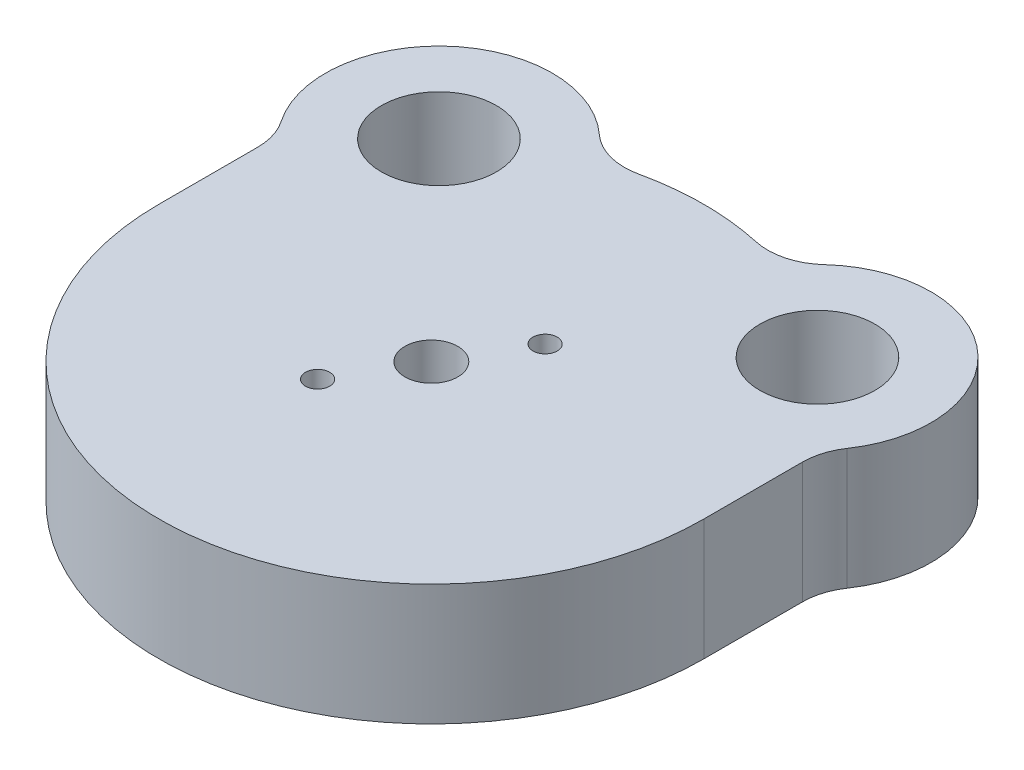
SolidWorks part; units mm, degrees
material "Plain Carbon Steel"
ref_plane "Front Plane" through (0, 0, 0) normal (0, 0, 1) x (1, 0, 0)
ref_plane "Top Plane" through (0, 0, 0) normal (0, 1, 0) x (1, 0, 0)
ref_plane "Right Plane" through (0, 0, 0) normal (1, 0, 0) x (0, 0, -1)
sketch "Sketch1" plane through (0, 0, 0) normal (0, 1, 0) x (1, 0, 0)
  line L0 (-100, 0) -> (100, 0) construction
  line L1 (0, -100) -> (0, 100) construction
  line L2 (-90, 0) -> (-90, 39.5049)
  line L3 (90, 0) -> (90, 39.5049)
  arc A0 (-90, 0) -> (90, 0) centre (0, 0) ccw
  arc A1 (-30.5618, 84.6521) -> (-90, 39.5049) centre (-62.5, 65) ccw
  arc A2 (90, 39.5049) -> (30.5618, 84.6521) centre (62.5, 65) ccw
  arc A3 (-30.5618, 84.6521) -> (-83.389, 33.8568) centre (0, 0) ccw construction
  arc A4 (-83.389, 33.8568) -> (-30.5618, 84.6521) centre (-62.5, 65) ccw construction
  arc A5 (30.5618, 84.6521) -> (-30.5618, 84.6521) centre (0, 0) ccw
  arc A6 (83.389, 33.8568) -> (30.5618, 84.6521) centre (0, 0) ccw construction
  arc A7 (30.5618, 84.6521) -> (83.389, 33.8568) centre (62.5, 65) ccw construction
  arc A8 (-83.389, 33.8568) -> (-90, 0) centre (0, 0) ccw construction
  arc A9 (90, 0) -> (83.389, 33.8568) centre (0, 0) ccw construction
  arc A10 (-90, 39.5049) -> (-83.389, 33.8568) centre (-62.5, 65) ccw construction
  arc A11 (83.389, 33.8568) -> (90, 39.5049) centre (62.5, 65) ccw construction
  dimension "D3" = 180
  dimension "D4" = 75
  dimension "D1" = 200
  dimension "D2" = 200
  dimension "D5" = 65
  dimension "D6" = 125
extrude "Boss-Extrude1" add sketch "Sketch1" along normal blind 40
sketch "Sketch2" plane through (0, 0, 0) normal (0, 1, 0) x (1, 0, 0)
  line L0 (-81.25, 32.524) -> (-59.2695, 19.8336)
  line L1 (-90, 39.5049) -> (-90, 0) construction
  line L2 (-90, 39.5049) -> (-90, 0)
  line L3 (0, -62.5) -> (0, 62.5) construction
  line L4 (81.25, 32.524) -> (59.2695, 19.8336)
  line L5 (90, 0) -> (90, 39.5049) construction
  line L6 (90, 0) -> (90, 39.5049)
  arc A0 (-59.2695, 19.8336) -> (59.2695, 19.8336) centre (0, 0) ccw
  arc A1 (-30.5618, 84.6521) -> (-90, 39.5049) centre (-62.5, 65) ccw construction
  arc A2 (-90, 39.5049) -> (-81.25, 32.524) centre (-62.5, 65) ccw
  arc A3 (-81.25, 32.524) -> (-69.2916, 28.1201) centre (-62.5, 65) ccw construction
  arc A4 (-30.5618, 84.6521) -> (-90, 39.5049) centre (-62.5, 65) ccw construction
  arc A5 (-90, 0) -> (90, 0) centre (0, 0) ccw construction
  arc A6 (-90, 0) -> (90, 0) centre (0, 0) ccw
  arc A7 (90, 39.5049) -> (81.25, 32.524) centre (62.5, 65) cw
  arc A8 (0, 62.5) -> (-59.2695, 19.8336) centre (0, 0) ccw construction
  arc A9 (59.2695, 19.8336) -> (0, 62.5) centre (0, 0) ccw construction
  dimension "D1" = 125
  dimension "D2" = 60
fillet "Fillet1" radius 20 4 edges at (30.5618, 20, -84.6521) (-30.5618, 20, -84.6521) (90, 20, -39.5049) (-90, 20, -39.5049)
sketch "Sketch3" plane through (0, 0, 0) normal (0, 1, 0) x (1, 0, 0)
  circle A0 centre (-62.5, 65) radius 19
  circle A1 centre (62.5, 65) radius 19
  dimension "D1" = 38
extrude "Cut-Extrude2" cut sketch "Sketch3" along normal up to next
hole_wizard "M20 Tapped Hole1" positions "Sketch7" profile "Sketch5" tap size "M20" standard "ISO" end condition through all
sketch "Sketch7" plane through (0, 40, 0) normal (0, 1, 0) x (1, 0, 0)
  point P0 (0, 0)
sketch "Sketch5" plane through (0, 40, 0) normal (1, 0, 0) x (0, 0, 1)
  line L0 (0, 0) -> (0, 40)
  line L1 (0, 40) -> (8.75, 40)
  line L2 (8.75, 40) -> (8.75, 0)
  line L5 (8.75, 0) -> (0, 0)
  line L11 (0, -6.35) -> (0, 107.95) construction
  dimension "Thru Tap Drill Dia." = 17.5
  dimension "Thru Tap Drill Depth" = 40
cosmetic thread "Hole Thread1"
sketch "Sketch8" plane through (0, 0, 0) normal (0, -1, 0) x (1, 0, 0)
  circle A0 centre (0, 0) radius 15
  dimension "D1" = 30
extrude "Cut-Extrude3" cut sketch "Sketch8" against normal blind 10
hole_wizard "M6 Tapped Hole1" positions "Sketch11" profile "Sketch10" tap size "M6" standard "ISO"
sketch "Sketch11" plane through (0, 0, 0) normal (0, -1, 0) x (-1, 0, 0)
  point P0 (-21.6506, -12.2377)
  point P3 (21.6506, -12.5)
  point P7 (0, 25)
sketch "Sketch10" plane through (21.6506, 0, 12.2377) normal (1, 0, 0) x (0, 0, -1)
  line L0 (0, 0) -> (0, 18.5022)
  line L1 (0, 18.5022) -> (2.5, 17)
  line L2 (2.5, 17) -> (2.5, 0)
  line L5 (2.5, 0) -> (0, 0)
  line L10 (0, 18.5022) -> (-2.5, 17) construction
  line L11 (0, -6.35) -> (0, 107.95) construction
  dimension "Tap Drill Dia." = 5
  dimension "Tap Drill Depth" = 17
  dimension "Drill Angle" = 118
cosmetic thread "Hole Thread2"
cosmetic thread "Hole Thread3"
cosmetic thread "Hole Thread4"
hole_wizard "Ø8.0mm Dowel Hole1" positions "Sketch14" profile "Sketch13" hole size "Ø8.0" standard "ISO" end condition through all
sketch "Sketch14" plane through (0, 0, 0) normal (0, -1, 0) x (-1, 0, 0)
  point P0 (13.75, -23.8157)
  point P3 (-13.75, 23.8157)
sketch "Sketch13" plane through (-13.75, 0, 23.8157) normal (1, 0, 0) x (0, 0, -1)
  line L0 (0, 0) -> (0, 40)
  line L1 (0, 40) -> (4, 40)
  line L2 (4, 40) -> (4, 0)
  line L5 (4, 0) -> (0, 0)
  line L11 (0, -6.35) -> (0, 107.95) construction
  dimension "Thru Hole Dia." = 8
  dimension "Thru Hole Depth" = 40
